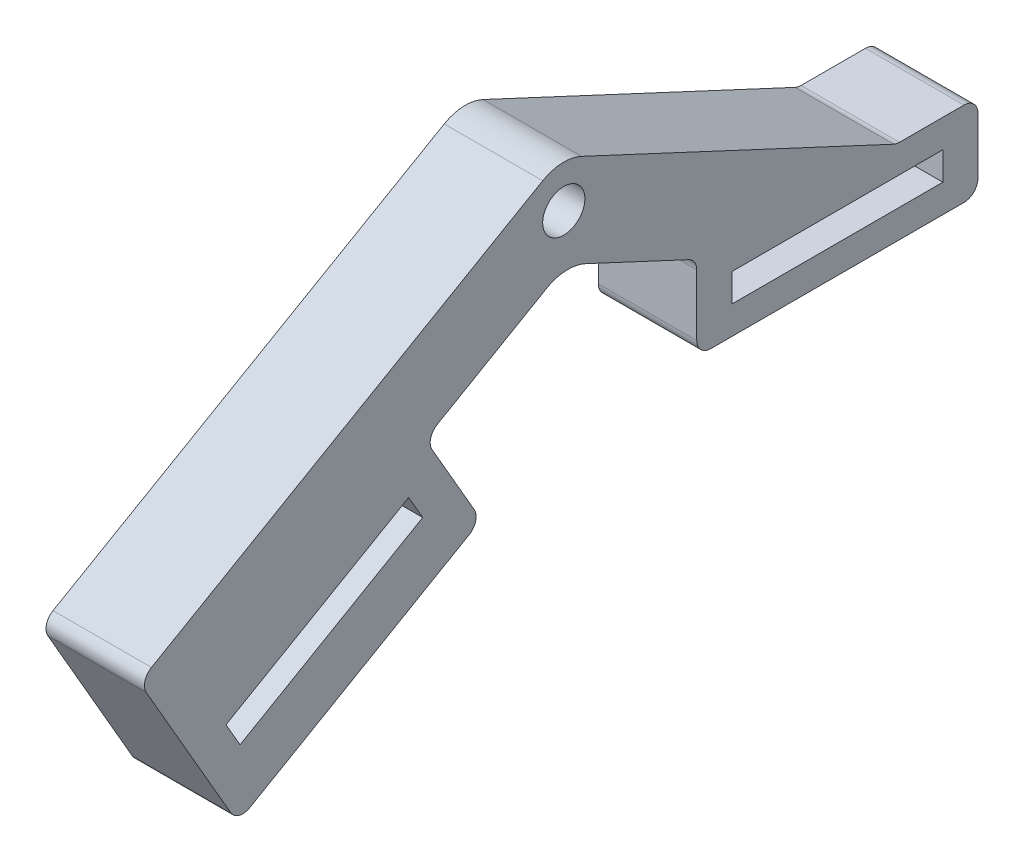
SolidWorks part; units mm, degrees
ref_plane "Alzado" through (0, 0, 0) normal (0, 0, 1) x (1, 0, 0)
ref_plane "Planta" through (0, 0, 0) normal (0, 1, 0) x (1, 0, 0)
ref_plane "Vista lateral" through (0, 0, 0) normal (1, 0, 0) x (0, 0, -1)
sketch "Croquis1" plane through (0, 0, 0) normal (1, 0, 0) x (0, 0, -1)
  line L0 (4.1972, 3) -> (-18.1868, 13.4378)
  line L1 (4.1972, 3) -> (10, 3)
  line L2 (-10, 3) -> (-10, -3)
  line L3 (-10, -3) -> (10, -3)
  line L4 (10, 3) -> (10, -3)
  line L5 (-10, 3) -> (10, -3) construction
  line L6 (-10, -3) -> (10, 3) construction
  line L7 (-7.5, 1) -> (7.5, 1)
  line L8 (-7.5, 1) -> (-7.5, -1)
  line L9 (-7.5, -1) -> (7.5, -1)
  line L10 (7.5, 1) -> (7.5, -1)
  line L11 (-7.5, 1) -> (7.5, -1) construction
  line L12 (-7.5, -1) -> (7.5, 1) construction
  line L13 (-10, 3) -> (-20.7225, 8) construction
  line L14 (-18.1868, 13.4378) -> (-20.7225, 8) construction
  line L15 (-10, 3) -> (4.1972, 3) construction
  line L16 (-19.4547, 10.7189) -> (-48.1404, -5.8428) construction
  line L17 (-20.9547, 13.317) -> (-49.6404, -3.2447)
  line L18 (-29.3199, 1.5591) -> (-20.6596, 6.5591)
  line L19 (-17.8918, 6.68) -> (-10, 3)
  line L20 (-29.3199, 1.5591) -> (-25.3199, -5.3691)
  line L21 (-25.3199, -5.3691) -> (-42.6404, -15.3691)
  line L22 (-42.6404, -15.3691) -> (-49.6404, -3.2447)
  line L23 (-30.4849, -1.4229) -> (-43.4753, -8.9229)
  line L24 (-29.4849, -3.155) -> (-42.4753, -10.655)
  line L25 (-29.4849, -3.155) -> (-30.4849, -1.4229)
  line L26 (-43.4753, -8.9229) -> (-42.4753, -10.655)
  arc A0 (-18.1868, 13.4378) -> (-20.9547, 13.317) centre (-19.4547, 10.7189) ccw
  circle A1 centre (-19.4547, 10.7189) radius 1.5
  arc A2 (-20.6596, 6.5591) -> (-17.8918, 6.68) centre (-19.1596, 3.9611) cw
  point P0 (0, 0)
  point P6 (0, 0)
  point P23 (-19.3072, 7.34)
  point P28 (-35.9801, -6.905)
  dimension "D9" = 3
  dimension "D12" = 3
  dimension "D1" = 6
  dimension "D2" = 20
  dimension "D3" = 2
  dimension "D4" = 15
  dimension "D5" = 2
  dimension "D6" = 6
  dimension "D7" = 25
  dimension "D8" = 5
  dimension "D10" = 35
  dimension "D11" = 6
  dimension "D13" = 10
  dimension "D14" = 8
  dimension "D15" = 20
  dimension "D16" = 4
  dimension "D17" = 2
  dimension "D18" = 15
  dimension "D19" = 10
extrude "Saliente-Extruir1" add sketch "Croquis1" along normal mid plane 7
fillet "Redondeo1" radius 1 9 edges at (0, 3, -10) (0, -3, -10) (0, -3, 10) (0, 3, 10) (0, 1.5591, 29.3199) (0, -5.3691, 25.3199) (0, -15.3691, 42.6404) (0, -3.2447, 49.6404) (0, 3, -4.1972)
